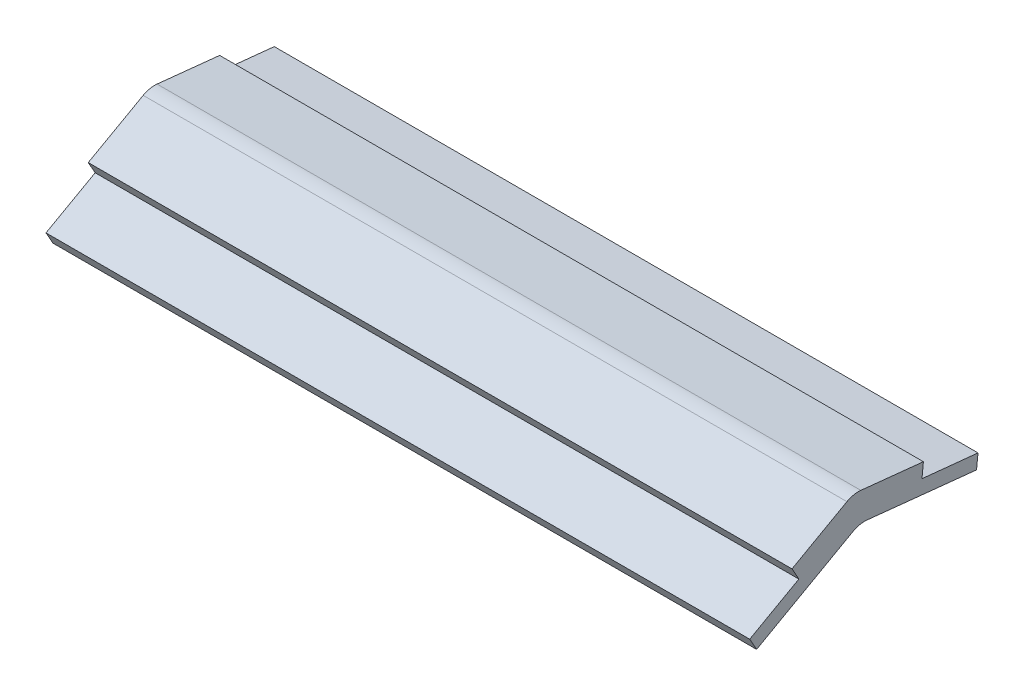
SolidWorks part; units mm, degrees
ref_plane "Front Plane" through (0, 0, 0) normal (0, 0, 1) x (1, 0, 0)
ref_plane "Top Plane" through (0, 0, 0) normal (0, 1, 0) x (1, 0, 0)
ref_plane "Right Plane" through (0, 0, 0) normal (1, 0, 0) x (0, 0, -1)
sketch "Sketch1" plane through (0, 0, 0) normal (1, 0, 0) x (0, 0, -1)
  line L6 (-17.0451, 11.0948) -> (-15.5805, 8.4766)
  line L7 (-17.0451, 11.0948) -> (-5.3363, 17.6448)
  line L8 (-2.3791, 18.2544) -> (10.9657, 16.8694)
  line L9 (10.9657, 16.8694) -> (10.6637, 13.8847)
  line L12 (-3.9542, 18.4179) -> (0, 0) construction
  line L13 (-15.5805, 8.4766) -> (-26.0533, 2.6182)
  line L14 (-26.0533, 2.6182) -> (-24.5887, 0)
  line L15 (-24.5887, 0) -> (-4.0185, 11.5069)
  line L16 (-1.0613, 12.1166) -> (22.293, 9.6927)
  line L18 (10.6637, 13.8847) -> (22.6027, 12.6767)
  line L19 (22.6027, 12.6767) -> (22.293, 9.6927)
  line L20 (0, 0) -> (50000, 0) construction
  arc A0 (-2.3791, 18.2544) -> (-5.3363, 17.6448) centre (-2.8952, 13.2811) ccw
  arc A1 (-1.0613, 12.1166) -> (-4.0185, 11.5069) centre (-1.5775, 7.1433) ccw
  point P23 (-2.6365, 12.2801)
  dimension "D12" = 5
  dimension "D13" = 5
  dimension "D1" = 15
  dimension "D2" = 15
  dimension "D3" = 145
  dimension "D5" = 12
  dimension "D6" = 12
  dimension "D7" = 3
  dimension "D8" = 3
  dimension "D9" = 3
  dimension "D10" = 3
extrude "Boss-Extrude1" add sketch "Sketch1" along normal blind 150
